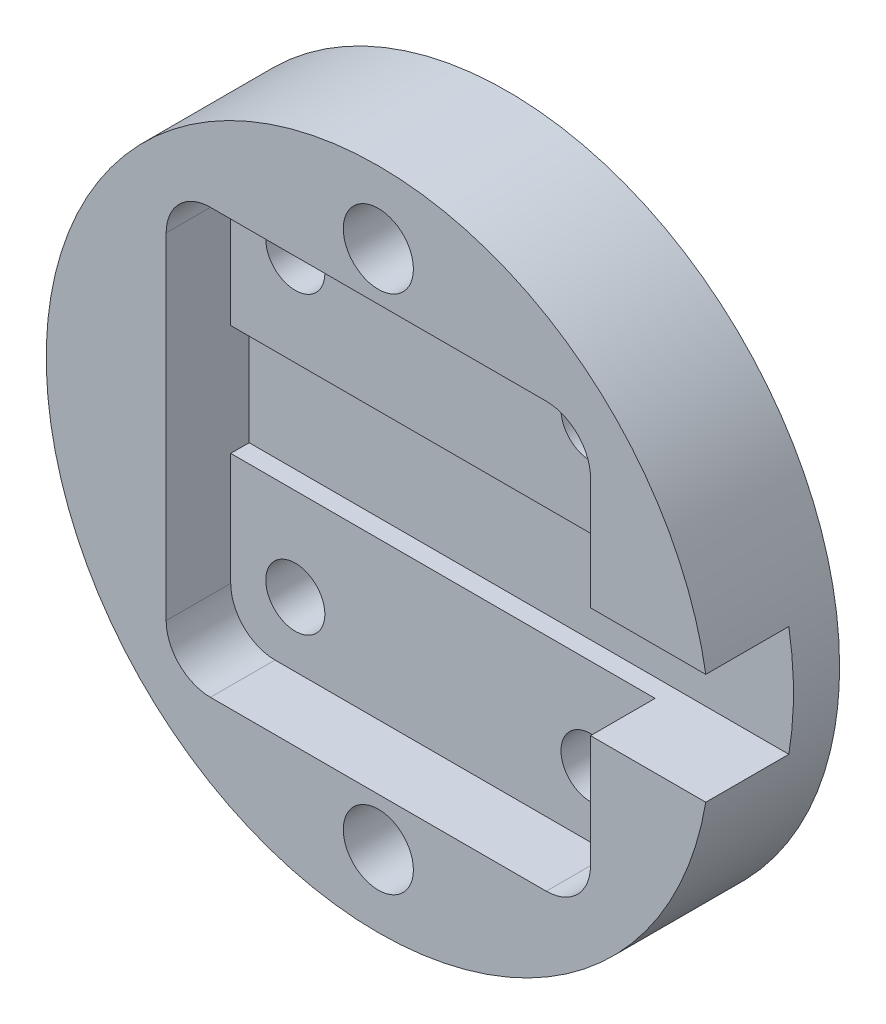
SolidWorks part; units mm, degrees
ref_plane "Front Plane" through (0, 0, 0) normal (1, 0, 0) x (0, 1, 0)
ref_plane "Top Plane" through (0, 0, 0) normal (0, 0, 1) x (0, 1, 0)
ref_plane "Right Plane" through (0, 0, 0) normal (0, 1, 0) x (-1, 0, 0)
sketch "Sketch1" plane through (0, 0, 0) normal (0, 0, 1) x (0, 1, 0)
  line L1 (-11.5, -11.5) -> (11.5, -11.5)
  line L2 (-11.5, -11.5) -> (-11.5, 11.5)
  line L3 (-11.5, 11.5) -> (11.5, 11.5)
  line L4 (11.5, -11.5) -> (11.5, 11.5)
  line L5 (-11.5, -11.5) -> (11.5, 11.5) construction
  line L6 (-11.5, 11.5) -> (11.5, -11.5) construction
  circle A0 centre (0, 0) radius 18
  circle A1 centre (-8, 8) radius 1.6
  circle A2 centre (8, 8) radius 1.6
  circle A3 centre (8, -8) radius 1.6
  circle A4 centre (-8, -8) radius 1.6
  circle A5 centre (14.1, 0) radius 1.9
  circle A6 centre (0, 0) radius 16 construction
  circle A7 centre (-14.1, 0) radius 1.9
  point P0 (0, 0)
  dimension "D1" = 36
  dimension "D3" = 3.2
  dimension "D5" = 16
  dimension "D6" = 32
  dimension "D7" = 3.8
  dimension "D2" = 23
  dimension "D4" = 4
extrude "Boss-Extrude1" add sketch "Sketch1" along normal blind 7 contours L1 L4 L3 L2 A4 A3 A2 A1 | A4 | A3 | A1 | A2 | A0 L4 L1 L2 L3 region at (0, 0, 0) region at (0, -17.4909, 0) region at (-8, -8, 0) region at (-8, 8, 0) region at (8, 8, 0) region at (8, -8, 0)
extrude "Cut-Extrude1" cut sketch "Sketch1<3>" against normal blind 3.5 from surface contours L1 L4 L3 L2 A4 A3 A2 A1 | A1 | A2 | A4 | A3 region at (0, 0, 0) region at (-8, -8, 0) region at (-8, 8, 0) region at (8, 8, 0) region at (8, -8, 0) starting at face at (1.9, -14.1, 7)
sketch "Sketch1<3>" plane through (0, 0, 0) normal (0, 0, 1) x (0, 1, 0) same geometry as "Sketch1"
extrude "Cut-Extrude3" cut sketch "Sketch1<4>" along normal through all contours A4 | A3 | A2 | A1 region at (-8, -8, 0) region at (-8, 8, 0) region at (8, 8, 0) region at (8, -8, 0)
sketch "Sketch1<4>" plane through (0, 0, 0) normal (0, 0, 1) x (0, 1, 0) same geometry as "Sketch1"
sketch "Sketch2" plane through (0, 0, 7) normal (0, 0, 1) x (1, 0, 0)
  line L0 (-11.5, 3) -> (17.7482, 3)
  line L1 (-11.5, 11.5) -> (-11.5, -11.5) construction
  line L2 (-11.5, -3) -> (17.7482, -3)
  line L5 (-11.5, 3) -> (-11.5, -3)
  circle A0 centre (0, 0) radius 18 construction
  arc A1 (17.7482, 3) -> (17.7482, -3) centre (0, 0) cw
  dimension "D1" = 6
extrude "Cut-Extrude4" cut sketch "Sketch2" against normal offset from surface (4.5 mm away) 1 up to face at (-9.6, -8, 3.5) offset beyond the face yes
fillet "Fillet1" radius 2.4 4 edges at (-11.5, -11.5, 5.25) (11.5, -11.5, 5.25) (11.5, 11.5, 5.25) (-11.5, 11.5, 5.25)
equation "\"AS5600Height\"=3.5"
equation "\"D1@Cut-Extrude1\"=\"AS5600Height\""
